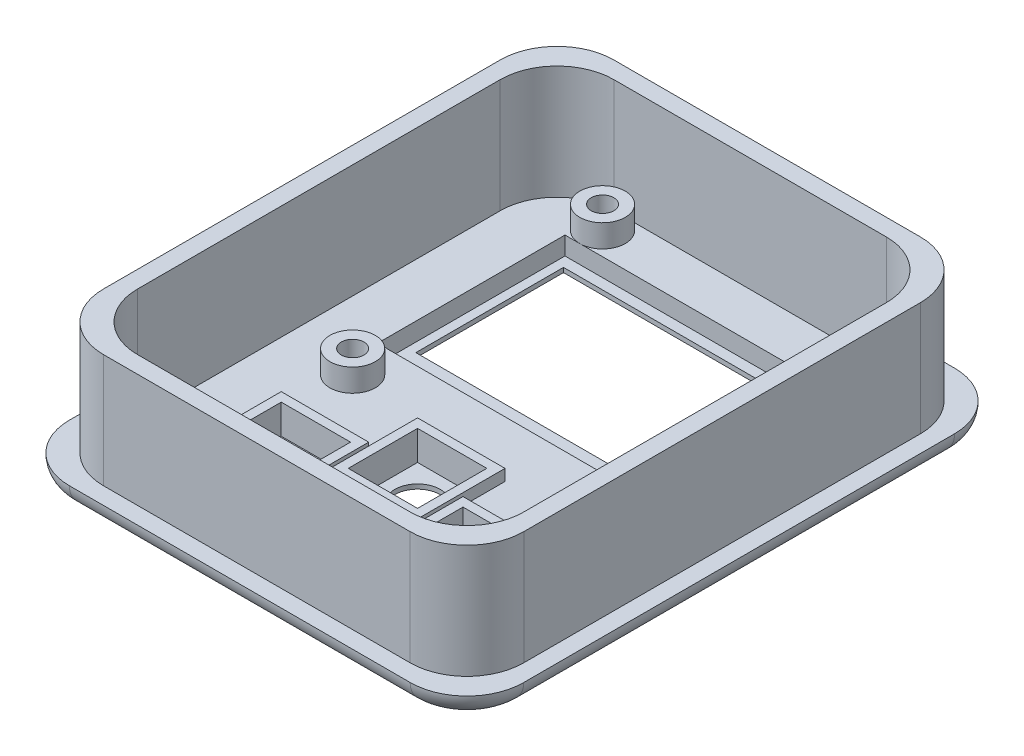
SolidWorks part; units mm, degrees
ref_plane "Piano frontale" through (0, 0, 0) normal (0, 0, 1) x (1, 0, 0)
ref_plane "Piano superiore" through (0, 0, 0) normal (0, 1, 0) x (1, 0, 0)
ref_plane "Piano destro" through (0, 0, 0) normal (1, 0, 0) x (0, 0, -1)
sketch "Schizzo1" plane through (0, 0, 0) normal (0, 1, 0) x (1, 0, 0)
  line L0 (-18.5, 22.465) -> (18.5, 22.465)
  line L1 (-20, 23.965) -> (20, 23.965)
  line L2 (-20, 23.965) -> (-20, -23.965)
  line L3 (-20, -23.965) -> (20, -23.965)
  line L4 (20, 23.965) -> (20, -23.965)
  line L5 (-20, 23.965) -> (20, -23.965) construction
  line L6 (-20, -23.965) -> (20, 23.965) construction
  line L7 (18.5, 22.465) -> (18.5, -22.465)
  line L8 (-18.5, -22.465) -> (18.5, -22.465)
  line L9 (-18.5, 22.465) -> (-18.5, -22.465)
  line L10 (-17, 20.965) -> (-17, -20.965)
  line L11 (-17, -20.965) -> (17, -20.965)
  line L12 (17, 20.965) -> (17, -20.965)
  line L13 (-17, 20.965) -> (17, 20.965)
  point P0 (0, 0)
  dimension "D1" = 47.93
  dimension "D2" = 40
  dimension "D3" = 1.5
  dimension "D4" = 3
extrude "Estrusione-Estrusione1" add sketch "Schizzo1" along normal blind 2 contours L3 L4 L1 L2
extrude "Estrusione-Estrusione2" add sketch "Schizzo1<3>" along normal blind 12 contours L10 L11 L12 L13 | L9 L8 L7 L0
sketch "Schizzo1<3>" plane through (0, 0, 0) normal (0, 1, 0) x (1, 0, 0) same geometry as "Schizzo1"
fillet "Raccordo1" radius 5 12 edges at (-18.5, 7, -22.465) (18.5, 7, -22.465) (18.5, 7, 22.465) (-18.5, 7, 22.465) (20, 1, 23.965) (-20, 1, 23.965) (-20, 1, -23.965) (20, 1, -23.965) (-17, 7, -20.965) (17, 7, -20.965) (17, 7, 20.965) (-17, 7, 20.965)
fillet "Raccordo2" radius 2 8 edges at (18.5355, 0, -22.5005) (0, 0, -23.965) (-18.5355, 0, -22.5005) (-20, 0, 0) (-18.5355, 0, 22.5005) (0, 0, 23.965) (18.5355, 0, 22.5005) (20, 0, 0)
sketch "Schizzo2" plane through (0, 0, 0) normal (0, 1, 0) x (1, 0, 0)
  line L1 (-11.5, 16.0323) -> (11.5, 16.0323)
  line L2 (-11.5, 16.0323) -> (-11.5, 3.0323)
  line L3 (-11.5, 3.0323) -> (11.5, 3.0323)
  line L4 (11.5, 16.0323) -> (11.5, 3.0323)
  line L5 (-11.5, 16.0323) -> (11.5, 3.0323) construction
  line L6 (-11.5, 3.0323) -> (11.5, 16.0323) construction
  line L7 (-3.85, -4.4648) -> (3.85, -4.4648)
  line L8 (-8, -8.3148) -> (8, -8.3148) construction
  line L9 (-8, -8.3148) -> (-8, -16.3148) construction
  line L10 (-8, -16.3148) -> (8, -16.3148) construction
  line L11 (8, -8.3148) -> (8, -16.3148) construction
  line L12 (-8, -8.3148) -> (8, -16.3148) construction
  line L13 (-8, -16.3148) -> (8, -8.3148) construction
  line L14 (-3.05, -5.2648) -> (3.05, -5.2648)
  line L15 (-3.05, -5.2648) -> (-3.05, -11.3648)
  line L16 (-3.05, -11.3648) -> (3.05, -11.3648)
  line L17 (3.05, -5.2648) -> (3.05, -11.3648)
  line L18 (-3.05, -5.2648) -> (3.05, -11.3648) construction
  line L19 (-3.05, -11.3648) -> (3.05, -5.2648) construction
  line L20 (11.05, -9.2648) -> (4.95, -9.2648)
  line L21 (11.05, -9.2648) -> (11.05, -15.3648)
  line L22 (11.05, -15.3648) -> (4.95, -15.3648)
  line L23 (4.95, -9.2648) -> (4.95, -15.3648)
  line L24 (11.05, -9.2648) -> (4.95, -15.3648) construction
  line L25 (11.05, -15.3648) -> (4.95, -9.2648) construction
  line L26 (-3.05, -13.2648) -> (3.05, -13.2648)
  line L27 (-3.05, -13.2648) -> (-3.05, -19.3648)
  line L28 (-3.05, -19.3648) -> (3.05, -19.3648)
  line L29 (3.05, -13.2648) -> (3.05, -19.3648)
  line L30 (-3.05, -13.2648) -> (3.05, -19.3648) construction
  line L31 (-3.05, -19.3648) -> (3.05, -13.2648) construction
  line L32 (-4.95, -9.2648) -> (-11.05, -9.2648)
  line L33 (-4.95, -9.2648) -> (-4.95, -15.3648)
  line L34 (-4.95, -15.3648) -> (-11.05, -15.3648)
  line L35 (-11.05, -9.2648) -> (-11.05, -15.3648)
  line L36 (-4.95, -9.2648) -> (-11.05, -15.3648) construction
  line L37 (-4.95, -15.3648) -> (-11.05, -9.2648) construction
  line L38 (3.85, -4.4648) -> (3.85, -12.1648)
  line L39 (-3.85, -12.1648) -> (3.85, -12.1648)
  line L40 (-3.85, -4.4648) -> (-3.85, -12.1648)
  line L41 (11.85, -8.4648) -> (4.15, -8.4648)
  line L42 (4.15, -8.4648) -> (4.15, -16.1648)
  line L43 (11.85, -16.1648) -> (4.15, -16.1648)
  line L44 (11.85, -8.4648) -> (11.85, -16.1648)
  line L45 (-3.85, -12.4648) -> (3.85, -12.4648)
  line L46 (3.85, -12.4648) -> (3.85, -20.1648)
  line L47 (-3.85, -20.1648) -> (3.85, -20.1648)
  line L48 (-3.85, -12.4648) -> (-3.85, -20.1648)
  line L49 (-4.15, -8.4648) -> (-4.15, -16.1648)
  line L50 (-4.15, -16.1648) -> (-11.85, -16.1648)
  line L51 (-11.85, -8.4648) -> (-11.85, -16.1648)
  line L52 (-4.15, -8.4648) -> (-11.85, -8.4648)
  circle A0 centre (0, -8.3148) radius 2
  circle A1 centre (8, -12.3148) radius 2
  circle A2 centre (0, -16.3148) radius 2
  circle A3 centre (-8, -12.3148) radius 2
  point P0 (0, 9.5323)
  point P8 (0, -12.3148)
  dimension "D5" = 6.1
  dimension "D1" = 23
  dimension "D2" = 13
  dimension "D3" = 16
  dimension "D4" = 8
  dimension "D6" = 6.1
  dimension "D7" = 0.8
extrude "Taglio-Estrusione1" cut sketch "Schizzo2" along normal through all both contours L2 L3 L4 L1 | A0 | A3 | A1 | A2
sketch "Schizzo3" plane through (0, 0, 0) normal (0, 1, 0) x (1, 0, 0)
  line L0 (-10.995, 18.965) -> (10.995, 18.965) construction
  line L1 (12, 20.965) -> (-12, 20.965) construction
  line L2 (-12.3, 16.965) -> (12.3, 16.965)
  line L3 (-12.3, 16.965) -> (-12.3, 0.465)
  line L4 (-12.3, 0.465) -> (12.3, 0.465)
  line L5 (12.3, 16.965) -> (12.3, 0.465)
  line L6 (-12.3, 16.965) -> (12.3, 0.465) construction
  line L7 (-12.3, 0.465) -> (12.3, 16.965) construction
  circle A0 centre (-10.995, 18.965) radius 2
  circle A1 centre (-10.995, 18.965) radius 0.9958
  circle A2 centre (10.995, 18.965) radius 2
  circle A3 centre (10.995, 18.965) radius 1
  circle A4 centre (-10.995, -3.035) radius 0.9958
  circle A5 centre (-10.995, -3.035) radius 2
  circle A6 centre (10.995, -3.035) radius 0.9958
  circle A7 centre (10.995, -3.035) radius 2
  point P6 (0, 18.965)
  point P7 (0, 8.715)
  dimension "D1" = 21.99
  dimension "D2" = 24.6
  dimension "D3" = 16.5
  dimension "D4" = 2
  dimension "D5" = 4
  dimension "D6" = 22
extrude "Taglio-Estrusione2" cut sketch "Schizzo3" along normal through all from offset 0.4 contours L3 L4 L5 L2 | A1 | A3
extrude "Estrusione-Estrusione3" add sketch "Schizzo3<3>" along normal blind 4 separate body contours A0 | A1 | A2 | A3 | A5 | A4 | A7 | A6
sketch "Schizzo3<3>" plane through (0, 0, 0) normal (0, 1, 0) x (1, 0, 0) same geometry as "Schizzo3"
extrude "Taglio-Estrusione3" cut sketch "Schizzo2<5>" along normal through all from offset 0.4 contours L17 L16 L15 L14 | L23 L22 L21 L20 | L29 L28 L27 L26 | L33 L34 L35 L32
sketch "Schizzo2<5>" plane through (0, 0, 0) normal (0, 1, 0) x (1, 0, 0) same geometry as "Schizzo2"
extrude "Estrusione-Estrusione4" add sketch "Schizzo2<6>" along normal blind 3 contours L51 L50 L49 L52 | L35 L34 L33 L32 | L40 L39 L38 L7 | L15 L16 L17 L14 | L42 L43 L44 L41 | L23 L22 L21 L20 | L29 L28 L27 L26 | L46 L47 L48 L45
sketch "Schizzo2<6>" plane through (0, 0, 0) normal (0, 1, 0) x (1, 0, 0) same geometry as "Schizzo2"
